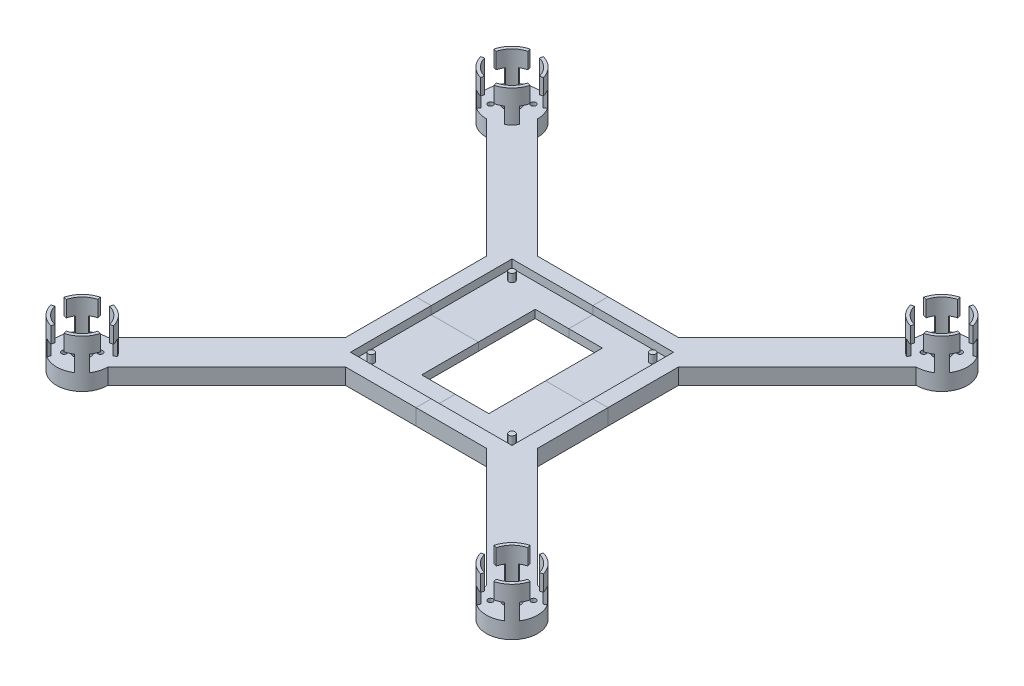
SolidWorks part; units mm, degrees
ref_plane "정면" through (0, 0, 0) normal (0, 0, 1) x (1, 0, 0)
ref_plane "윗면" through (0, 0, 0) normal (0, 1, 0) x (1, 0, 0)
ref_plane "우측면" through (0, 0, 0) normal (1, 0, 0) x (0, 0, -1)
sketch "스케치1" plane through (0, 0, 0) normal (0, 1, 0) x (1, 0, 0)
  line L5 (134.3503, -118.3503) -> (60, -44)
  line L6 (-44, 60) -> (44, 60)
  line L8 (-60, 44) -> (-60, -44)
  line L9 (-44, -60) -> (44, -60)
  line L10 (60, 44) -> (60, -44)
  line L11 (-60, 60) -> (60, -60) construction
  line L18 (-60, -60) -> (60, 60) construction
  line L19 (60, -44) -> (44, -60) construction
  line L20 (44, -60) -> (118.3503, -134.3503)
  line L21 (-118.3503, -134.3503) -> (-44, -60)
  line L22 (-60, -44) -> (-134.3503, -118.3503)
  line L23 (-134.3503, 118.3503) -> (-60, 44)
  line L24 (-44, 60) -> (-118.3503, 134.3503)
  line L25 (118.3503, 134.3503) -> (44, 60)
  line L26 (60, 44) -> (134.3503, 118.3503)
  line L27 (-60, -60) -> (-44, -60) construction
  line L28 (-60, -44) -> (-60, -60) construction
  line L29 (44, -60) -> (60, -60) construction
  line L30 (60, -44) -> (60, -60) construction
  line L31 (44, 60) -> (60, 60) construction
  line L32 (60, 60) -> (60, 44) construction
  line L33 (-60, 60) -> (-44, 60) construction
  line L34 (-60, 60) -> (-60, 44) construction
  line L35 (134.3503, 134.3503) -> (35489.6893, -35220.9888) construction
  line L36 (-134.3503, 134.3503) -> (-35489.6893, -35220.9888) construction
  line L37 (-134.3503, -134.3503) -> (-122.3295, -146.3711) construction
  line L38 (-21, 35.5) -> (21, 35.5)
  line L39 (-21, 35.5) -> (-21, -35.5)
  line L40 (-21, -35.5) -> (21, -35.5)
  line L41 (21, 35.5) -> (21, -35.5)
  line L42 (-21, 35.5) -> (21, -35.5) construction
  line L43 (-21, -35.5) -> (21, 35.5) construction
  line L44 (134.3503, -134.3503) -> (35489.6893, 35220.9888) construction
  arc A5 (118.3503, -134.3503) -> (134.3503, -118.3503) centre (134.3503, -134.3503) ccw
  arc A6 (123.0366, -123.0366) -> (118.3503, -134.3503) centre (134.3503, -134.3503) ccw construction
  arc A7 (134.3503, -118.3503) -> (123.0366, -123.0366) centre (134.3503, -134.3503) ccw construction
  arc A8 (-134.3503, -118.3503) -> (-118.3503, -134.3503) centre (-134.3503, -134.3503) ccw
  arc A9 (-123.0366, -123.0366) -> (-134.3503, -118.3503) centre (-134.3503, -134.3503) ccw construction
  arc A10 (-118.3503, -134.3503) -> (-123.0366, -123.0366) centre (-134.3503, -134.3503) ccw construction
  arc A11 (-118.3503, 134.3503) -> (-134.3503, 118.3503) centre (-134.3503, 134.3503) ccw
  arc A12 (-123.0366, 123.0366) -> (-118.3503, 134.3503) centre (-134.3503, 134.3503) ccw construction
  arc A13 (-134.3503, 118.3503) -> (-123.0366, 123.0366) centre (-134.3503, 134.3503) ccw construction
  arc A14 (134.3503, 118.3503) -> (145.664, 123.0366) centre (134.3503, 134.3503) ccw
  arc A15 (123.0366, 123.0366) -> (134.3503, 118.3503) centre (134.3503, 134.3503) ccw construction
  arc A16 (118.3503, 134.3503) -> (123.0366, 123.0366) centre (134.3503, 134.3503) ccw construction
  circle A49 centre (134.3503, 134.3503) radius 5.1
  circle A50 centre (140.0071, 140.0071) radius 1.65
  circle A51 centre (141.0678, 127.6328) radius 1.65
  circle A53 centre (127.6328, 141.0678) radius 1.65
  circle A54 centre (128.6934, 128.6934) radius 1.65
  circle A58 centre (134.3503, -134.3503) radius 5.1
  circle A59 centre (140.0071, -140.0071) radius 1.65
  circle A60 centre (127.6328, -141.0678) radius 1.65
  circle A61 centre (141.0678, -127.6328) radius 1.65
  circle A62 centre (128.6934, -128.6934) radius 1.65
  circle A63 centre (-134.3503, -134.3503) radius 5.1
  circle A64 centre (134.3503, 134.3503) radius 16 construction
  arc A65 (145.664, 123.0366) -> (145.664, 145.664) centre (134.3503, 134.3503) ccw
  circle A66 centre (134.3503, 134.3503) radius 16 construction
  circle A67 centre (134.3503, 134.3503) radius 16 construction
  arc A68 (123.0366, 145.664) -> (118.3503, 134.3503) centre (134.3503, 134.3503) ccw
  circle A69 centre (134.3503, 134.3503) radius 16 construction
  circle A70 centre (134.3503, 134.3503) radius 16 construction
  arc A71 (145.664, 145.664) -> (123.0366, 145.664) centre (134.3503, 134.3503) ccw
  circle A72 centre (134.3503, 134.3503) radius 16 construction
  circle A75 centre (-140.0071, -140.0071) radius 1.65
  circle A76 centre (-141.0678, -127.6328) radius 1.65
  circle A77 centre (-127.6328, -141.0678) radius 1.65
  circle A78 centre (-128.6934, -128.6934) radius 1.65
  circle A79 centre (-134.3503, 134.3503) radius 5.1
  circle A80 centre (-140.0071, 140.0071) radius 1.65
  circle A81 centre (-127.6328, 141.0678) radius 1.65
  circle A82 centre (-141.0678, 127.6328) radius 1.65
  circle A83 centre (-128.6934, 128.6934) radius 1.65
  point P0 (0, 0)
  point P36 (0, 0)
  dimension "D4" = 190
  dimension "D5" = 71
  dimension "D6" = 42
  dimension "D3" = 4
  dimension "D9" = 8
  dimension "D11" = 3.3
  dimension "D12" = 9.5
  dimension "D13" = 16
  dimension "D15" = 2
  dimension "D7" = 10.2
  dimension "D10" = 3.3
  dimension "D16" = 9.5
  dimension "D1" = 120
  dimension "D2" = 120
  dimension "D8" = 4
extrude "보스-돌출2" add sketch "스케치1" against normal blind 10
sketch "스케치2" plane through (0, 0, 0) normal (0, 1, 0) x (1, 0, 0)
  line L1 (-50.5, 50.5) -> (50.5, 50.5)
  line L2 (-50.5, 50.5) -> (-50.5, -50.5)
  line L3 (-50.5, -50.5) -> (50.5, -50.5)
  line L4 (50.5, 50.5) -> (50.5, -50.5)
  line L5 (-50.5, 50.5) -> (50.5, -50.5) construction
  line L6 (-50.5, -50.5) -> (50.5, 50.5) construction
  point P0 (0, 0)
  dimension "D1" = 101
  dimension "D2" = 101
extrude "컷-돌출1" cut sketch "스케치2" against normal blind 5
sketch "스케치3" plane through (0, 0, 0) normal (0, 1, 0) x (1, 0, 0)
  line L1 (-44, 44) -> (44, 44) construction
  line L2 (-44, 44) -> (-44, -44) construction
  line L3 (-44, -44) -> (44, -44) construction
  line L4 (44, 44) -> (44, -44) construction
  line L5 (-44, 44) -> (44, -44) construction
  line L6 (-44, -44) -> (44, 44) construction
  circle A0 centre (-44, 44) radius 1.9
  circle A1 centre (44, 44) radius 1.9
  circle A2 centre (-44, -44) radius 1.9
  circle A3 centre (44, -44) radius 1.9
  point P0 (0, 0)
  dimension "D3" = 3.8
  dimension "D1" = 88
  dimension "D2" = 88
extrude "보스-돌출3" add sketch "스케치3" along normal blind 5 from surface starting at face at (0, -5, 0)
sketch "스케치5" plane through (0, 0, 0) normal (0, 1, 0) x (1, 0, 0)
  line L0 (134.5732, 134.1274) -> (35489.9122, -35221.2117) construction
  line L1 (134.3503, 134.3503) -> (35489.6893, 35489.6893) construction
  line L2 (-865.6497, 134.3503) -> (49134.3503, 134.3503) construction
  circle A0 centre (134.3503, 134.3503) radius 16
  circle A1 centre (134.3503, 134.3503) radius 14
  dimension "D1" = 32
  dimension "D2" = 28
  dimension "D3" = 45
  dimension "D4" = 45
extrude "보스-돌출4" add sketch "스케치5" along normal blind 20
sketch "스케치6" plane through (0, 0, 0) normal (0, 1, 0) x (1, 0, 0)
  line L0 (697.887, -730.2018) -> (143.0873, 120.9464) construction
  line L1 (972.0946, -411.7124) -> (134.3503, 134.3503) construction
  line L2 (134.3503, 134.3503) -> (134.3503, -49865.6497) construction
  line L3 (-730.2018, -429.1865) -> (120.9464, 125.6133) construction
  line L4 (-429.1865, -730.2018) -> (125.6133, 120.9464) construction
  line L9 (125.6133, 147.7542) -> (134.3503, 134.3503)
  line L10 (147.7542, 125.6133) -> (134.3503, 134.3503)
  line L11 (134.3503, 134.3503) -> (147.7542, 143.0873)
  line L12 (143.0873, 147.7542) -> (134.3503, 134.3503)
  line L13 (120.9464, 143.0873) -> (-41752.864, 27437.4872) construction
  line L14 (134.3503, 134.3503) -> (42021.5645, 27437.4872) construction
  line L15 (134.3503, 134.3503) -> (-27168.7866, 42021.5645) construction
  line L16 (134.3503, 134.3503) -> (27437.4872, 42021.5645) construction
  line L17 (143.0873, 120.9464) -> (134.3503, 134.3503)
  line L18 (125.6133, 120.9464) -> (134.3503, 134.3503)
  line L19 (120.9464, 125.6133) -> (134.3503, 134.3503)
  line L20 (120.9464, 143.0873) -> (134.3503, 134.3503)
  circle A0 centre (134.3503, 134.3503) radius 16 construction
  arc A1 (120.9464, 143.0873) -> (120.9464, 125.6133) centre (134.3503, 134.3503) ccw
  arc A2 (143.0873, 147.7542) -> (125.6133, 147.7542) centre (134.3503, 134.3503) ccw
  arc A3 (147.7542, 125.6133) -> (147.7542, 143.0873) centre (134.3503, 134.3503) ccw
  arc A4 (125.6133, 120.9464) -> (143.0873, 120.9464) centre (134.3503, 134.3503) ccw
  circle A5 centre (140.0071, 140.0071) radius 1.65 construction
extrude "컷-돌출2" cut sketch "스케치6" along normal blind 10 contours L20 A1 L19 | L18 A4 L17 | L10 A3 L11 | L12 A2 L9 region at (134.3503, 0, -144.4336) region at (144.4336, 0, -134.3503) region at (134.3503, 0, -124.267) region at (124.267, 0, -134.3503)
sketch "스케치8" plane through (0, 0, 0) normal (0, 1, 0) x (1, 0, 0)
  line L0 (134.3503, 134.3503) -> (118.8955, 130.2092)
  line L1 (134.3503, 134.3503) -> (118.8955, 138.4914)
  line L2 (134.3503, 134.3503) -> (149.8051, 130.2092)
  line L3 (134.3503, 134.3503) -> (149.8051, 138.4914)
  line L4 (134.3503, 134.3503) -> (138.4914, 118.8955)
  line L5 (134.3503, 134.3503) -> (130.2092, 118.8955)
  line L6 (134.3503, 134.3503) -> (138.4914, 149.8051)
  line L7 (134.3503, 134.3503) -> (130.2092, 149.8051)
  line L8 (136.3657, 134.3503) -> (50136.3657, 134.3503) construction
  line L9 (134.3503, 138.8006) -> (134.3503, 50138.8006) construction
  circle A0 centre (134.3503, 134.3503) radius 16 construction
  arc A1 (118.8955, 138.4914) -> (118.8955, 130.2092) centre (134.3503, 134.3503) ccw
  arc A2 (138.4914, 149.8051) -> (130.2092, 149.8051) centre (134.3503, 134.3503) ccw
  arc A3 (149.8051, 130.2092) -> (149.8051, 138.4914) centre (134.3503, 134.3503) ccw
  arc A4 (130.2092, 118.8955) -> (138.4914, 118.8955) centre (134.3503, 134.3503) ccw
  point P2 (118.3503, 134.3503)
  point P11 (134.3503, 150.3503)
  dimension "D1" = 30
  dimension "D2" = 30
extrude "컷-돌출3" cut sketch "스케치8" along normal through all contours L1 A1 L0 | L2 A3 L3 | L6 A2 L7 | L5 A4 L4 region at (123.8051, 0, -134.3503) region at (144.8955, 0, -134.3503) region at (134.3503, 0, -123.8051) region at (134.3503, 0, -144.8955)
ref_axis "기준축1" through (0, 21.5, 0) along (0, -1, 0)
pattern_circular "원형 패턴4" count 4 over 360 about axis through (0, 21.5, 0) along (0, -1, 0) of "보스-돌출4", "컷-돌출3", "컷-돌출2"
sketch "스케치9" plane through (0, 0, 0) normal (0, 1, 0) x (1, 0, 0)
  line L0 (-60, 0) -> (60, 0)
  line L1 (-60, 44) -> (-60, -44) construction
  line L2 (60, -44) -> (60, 44) construction
  line L3 (0, -60) -> (0, 60)
  line L4 (-44, -60) -> (44, -60) construction
  line L5 (44, 60) -> (-44, 60) construction
split "분할2" trim tools "스케치9" bodies to split 112 resulting bodies 124 125 126 127
ref_plane "평면1" through (0, 0, 0) normal (-0.7071, 0, -0.7071) x (-0.7071, 0, 0.7071)
